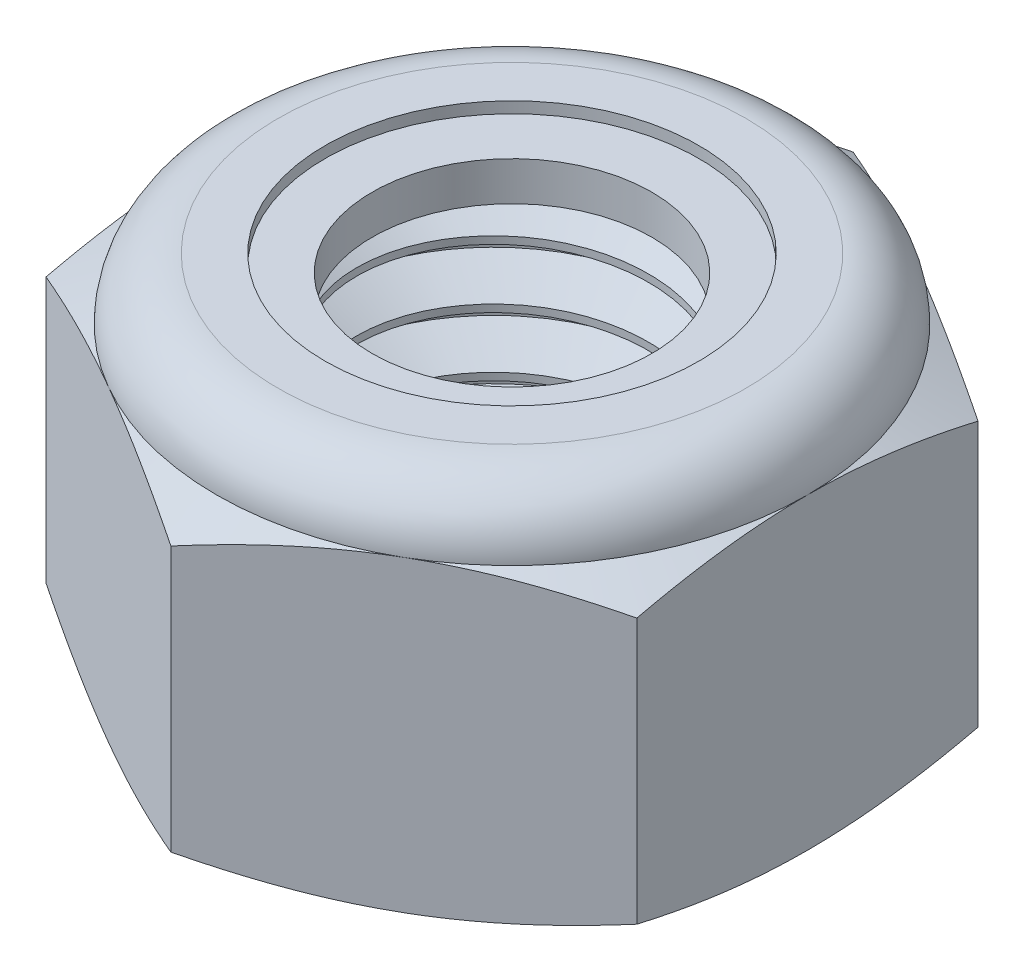
SolidWorks part; units mm, degrees
ref_plane "Front" through (0, 0, 0) normal (0, 0, 1) x (1, 0, 0)
ref_plane "Top" through (0, 0, 0) normal (0, 1, 0) x (1, 0, 0)
ref_plane "Right" through (0, 0, 0) normal (1, 0, 0) x (0, 0, -1)
sketch "Sketch1" plane through (0, 0, 0) normal (0, 1, 0) x (1, 0, 0)
  line L1 (0, 4.6188) -> (-4, 2.3094)
  line L2 (-4, 2.3094) -> (-4, -2.3094)
  line L3 (-4, -2.3094) -> (0, -4.6188)
  line L4 (0, -4.6188) -> (4, -2.3094)
  line L5 (4, -2.3094) -> (4, 2.3094)
  line L6 (4, 2.3094) -> (0, 4.6188)
  circle A0 centre (0, 0) radius 4 construction
  dimension "Hex Flats" = 8
extrude "Extrude1" add sketch "Sketch1" along normal blind 5
sketch "Sketch2" plane through (0, 0, 0) normal (1, 0, 0) x (0, 0, -1)
  line L0 (-2.5, 0) -> (-2.5, 5) construction
  line L1 (0, 0) -> (2.5, 0)
  line L2 (0, 0) -> (0, 5)
  line L3 (0, 5) -> (2.5, 5)
  line L4 (2.5, 0) -> (2.5, 5)
  line L5 (-2.3094, 5) -> (2.3094, 5) construction
  line L7 (0, -2.5) -> (0, 0) construction
  dimension "Thread Dia" = 5
revolve "Revolve1" add sketch "Sketch2" angle 360 about L7
sketch "Sketch8" plane through (0, 0, 0) normal (0, -1, 0) x (1, 0, 0)
  circle A1 centre (0, 0) radius 2.5
  circle A2 centre (0, 0) radius 2.5
  dimension "D1" = 0
curve "Helix/Spiral1" pitch 0.8 height 5.8 turns 7.25 parameters "Pitch"=0.8
sketch "Sketch10" plane through (0, 0, 0) normal (0, -1, 0) x (1, 0, 0)
  circle A1 centre (0, 0) radius 2.5
  circle A2 centre (0, 0) radius 2.5
  dimension "D1" = 0
extrude "Boss-Extrude1" add sketch "Sketch10" against normal through all draft 45
sketch "Sketch11" plane through (0, 5, 0) normal (0, 1, 0) x (1, 0, 0)
  circle A1 centre (0, 0) radius 2.5
  circle A2 centre (0, 0) radius 2.5
  dimension "D1" = 0
extrude "Boss-Extrude2" add sketch "Sketch11" against normal through all draft 45
sketch "Sketch9" plane through (0, 0, 0) normal (1, 0, 0) x (0, 0, -1)
  line L0 (2.5, -0.7) -> (2.5, 0)
  line L1 (2.5, -0.7) -> (1.9804, -0.4)
  line L2 (1.9804, -0.4) -> (1.9804, -0.3)
  line L3 (1.9804, -0.3) -> (2.5, 0)
  line L4 (-2.5, 0) -> (2.5, 0) construction
  line L5 (2.5, -0.35) -> (1.9804, -0.35) construction
  line L6 (2.2402, -0.55) -> (2.2402, -0.15) construction
  dimension "D1" = 0.1
  dimension "D2" = 0.4
  dimension "D3" = 60
sweep "Cut-Sweep1" cut profiles "Sketch9" path "Helix/Spiral1"
combine bodies "Combine1" operation type subtract main body 108 bodies to subtract 132
sketch "Sketch5" plane through (0, 0, 0) normal (1, 0, 0) x (0, 0, -1)
  line L0 (0, 0) -> (4, 0)
  line L1 (4, 0) -> (4.6188, 0.2886)
  line L2 (4.6188, 0.2886) -> (4.6188, 3.8781)
  line L3 (4.6188, 3.8781) -> (4, 4.1667)
  line L4 (3.1667, 5) -> (3.1667, 6.27)
  line L5 (3.1667, 6.27) -> (5.8888, 6.27)
  line L6 (5.8888, 6.27) -> (5.8888, -1.27)
  line L7 (5.8888, -1.27) -> (0, -1.27)
  line L8 (0, -1.27) -> (0, 0)
  line L9 (4, 4.1667) -> (4, 0) construction
  line L10 (0, 0) -> (2.5, 0) construction
  line L13 (4.6188, 2.0833) -> (5.8888, 2.0833) construction
  line L14 (4.6188, 5) -> (4.6188, 0) construction
  line L15 (0, 0) -> (0, 6.27) construction
  line L20 (0, 6.27) -> (3.1667, 6.27) construction
  line L22 (0, 5) -> (2.5, 5) construction
  arc A0 (4, 4.1667) -> (3.1667, 5) centre (3.1667, 4.1667) ccw
  dimension "D1" = 25
  dimension "D2" = 1.27
  dimension "D3" = 5
  dimension "D4" = 0.8333
revolve "Cut-Revolve3" cut sketch "Sketch5" angle 360 about L15
sketch "Sketch6" plane through (0, 0, 0) normal (1, 0, 0) x (0, 0, -1)
  line L0 (0, 4.1667) -> (3.8476, 4.1667)
  line L1 (3.1667, 4.8476) -> (2.5302, 4.8476)
  line L2 (0, 6.27) -> (0, 4.1667)
  line L3 (2.5302, 6.27) -> (0, 6.27)
  line L4 (0, 6.27) -> (3.1667, 6.27) construction
  line L5 (0, 0) -> (0, 6.27) construction
  line L6 (0, 6.27) -> (0, 0) construction
  line L7 (2.5302, 4.8476) -> (2.5302, 6.27)
  line L8 (3.1667, 5) -> (3.1667, 4.8476) construction
  line L9 (2.5302, 4.8476) -> (1.8938, 4.8476) construction
  line L10 (1.8938, 4.8476) -> (1.8938, 0) construction
  line L13 (1.8938, 4.55) -> (2.5, 4.2) construction
  line L15 (2.5, 0) -> (2.5, 5) construction
  line L16 (1.8938, 4.65) -> (2.5, 5) construction
  line L19 (2.1969, 4.375) -> (2.1969, 4.825) construction
  line L20 (1.8938, 4.55) -> (1.8938, 4.65) construction
  line L21 (2.5, 4.2) -> (2.5, 5) construction
  line L22 (2.5, 4.6) -> (1.8938, 4.6) construction
  arc A0 (3.8476, 4.1667) -> (3.1667, 4.8476) centre (3.1667, 4.1667) ccw
  arc A1 (4, 4.1667) -> (3.1667, 5) centre (3.1667, 4.1667) ccw construction
  dimension "D1" = 0.1524
  dimension "D2" = 0.8
  dimension "D3" = 0.1
  dimension "D4" = 60
revolve "Cut-Revolve4" cut sketch "Sketch6" angle 360 about L6
sketch "Sketch7" plane through (0, 0, 0) normal (1, 0, 0) x (0, 0, -1)
  line L0 (1.8938, 4.2429) -> (3.7666, 4.2429)
  line L1 (3.1667, 4.7714) -> (1.8938, 4.7714)
  line L2 (1.8938, 4.7714) -> (1.8938, 4.2429)
  line L3 (1.8938, 4.2429) -> (0, 4.2429) construction
  line L4 (0, 4.2429) -> (0, 4.7714) construction
  line L5 (0, 4.7714) -> (1.8938, 4.7714) construction
  line L6 (1.8938, 4.2429) -> (1.8938, 4.1667) construction
  line L7 (0, 4.1667) -> (3.8476, 4.1667) construction
  line L8 (3.1667, 4.7714) -> (3.1667, 4.8476) construction
  line L9 (1.8938, 4.8476) -> (1.8938, 0) construction
  arc A0 (3.7666, 4.2429) -> (3.1667, 4.7714) centre (3.1667, 4.1667) ccw
  arc A2 (3.8476, 4.1667) -> (3.1667, 4.8476) centre (3.1667, 4.1667) ccw construction
  dimension "D1" = 0.0762
revolve "Revolve2" add sketch "Sketch7" angle 360 about L4
equation "\"D4@Sketch5\"=\"Height@Extrude1\"/6"
equation "\"D3@Helix/Spiral1\"=\"Pitch@Helix/Spiral1\"+\"Height@Extrude1\""
equation "\"D1@Sketch9\"=\"Pitch@Helix/Spiral1\"*.125"
equation "\"D2@Sketch9\"=\"Pitch@Helix/Spiral1\"*.50"
equation "\"D2@Sketch6\"=\"Pitch@Helix/Spiral1\""
equation "\"D3@Sketch6\"=\"Pitch@Helix/Spiral1\"/8"
